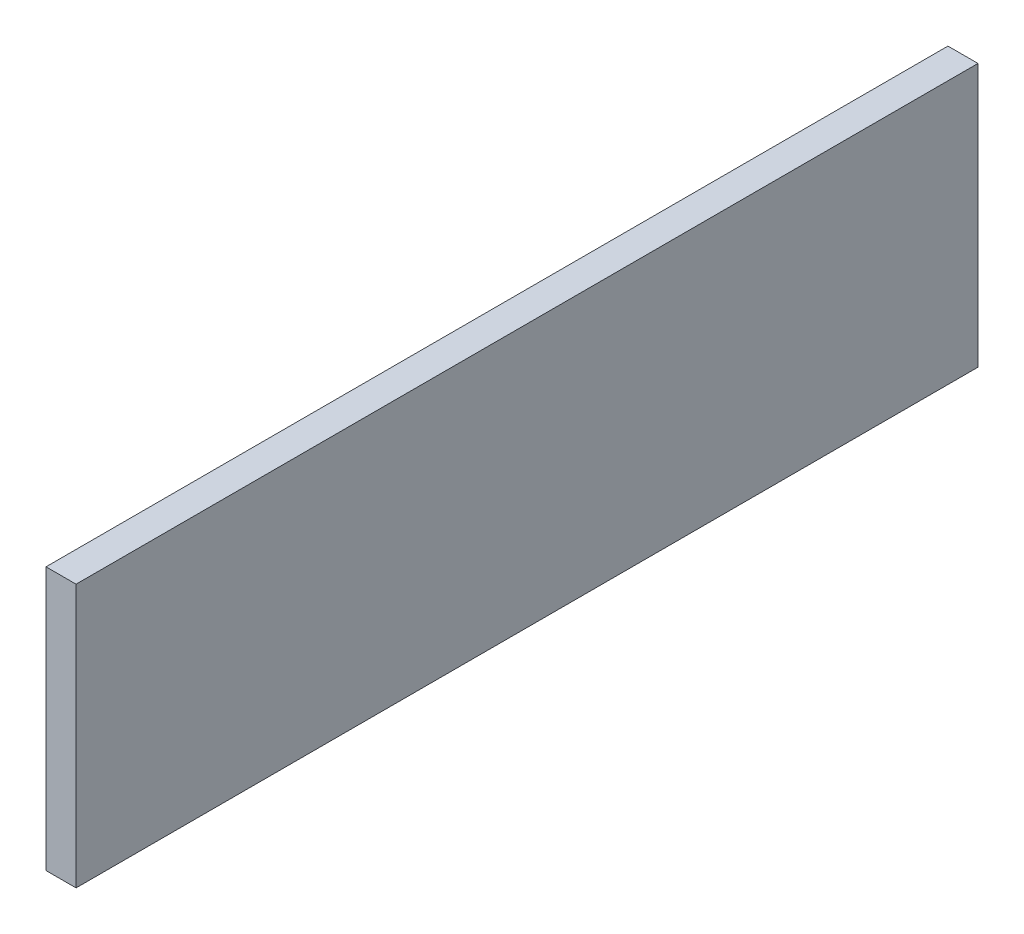
SolidWorks part; units mm, degrees
ref_plane "Front Plane" through (0, 0, 0) normal (0, 0, 1) x (1, 0, 0)
ref_plane "Top Plane" through (0, 0, 0) normal (0, 1, 0) x (1, 0, 0)
ref_plane "Right Plane" through (0, 0, 0) normal (1, 0, 0) x (0, 0, -1)
sketch "Sketch1" plane through (0, 0, 0) normal (1, 0, 0) x (0, 0, -1)
  line L1 (-551.8519, 418.0556) -> (648.1481, 418.0556)
  line L2 (-551.8519, 418.0556) -> (-551.8519, 68.0556)
  line L3 (-551.8519, 68.0556) -> (648.1481, 68.0556)
  line L4 (648.1481, 418.0556) -> (648.1481, 68.0556)
  dimension "D1" = 1200
  dimension "D2" = 350
extrude "Boss-Extrude1" add sketch "Sketch1" along normal blind 40
